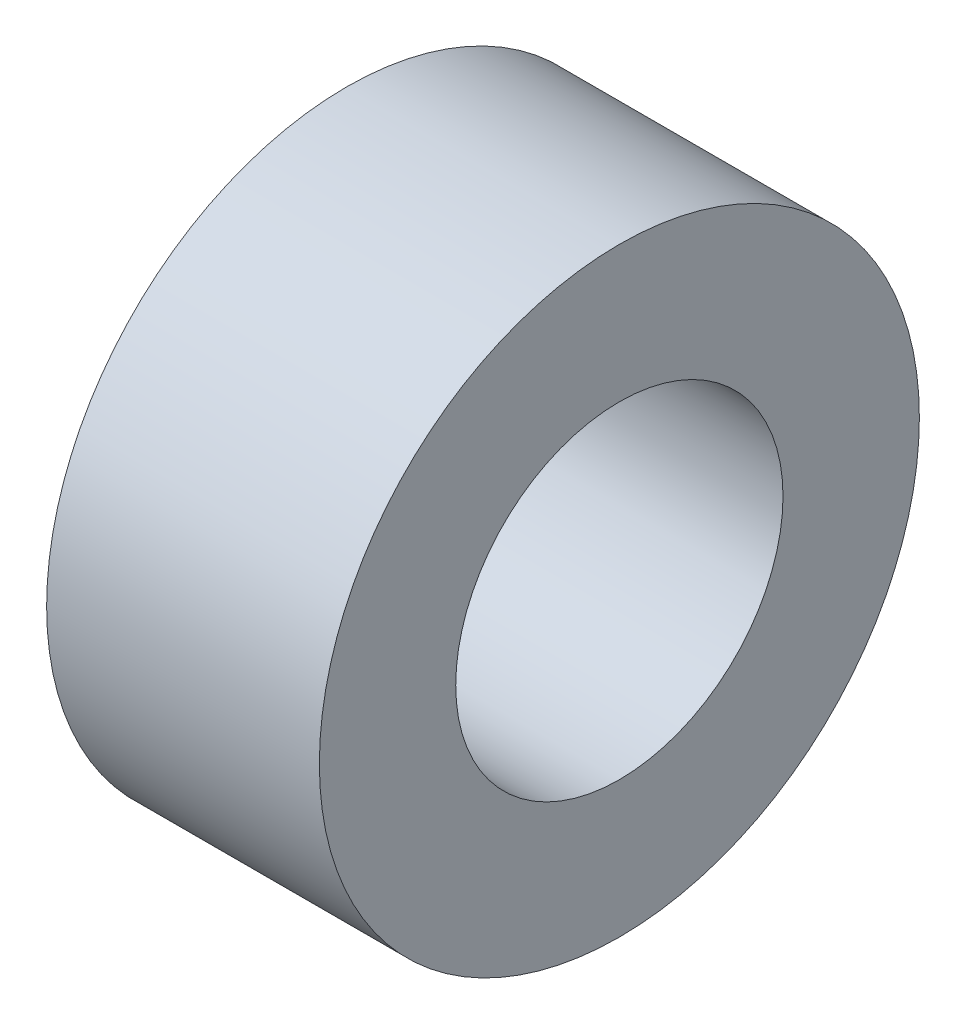
SolidWorks part; units mm, degrees
ref_plane "前视基准面" through (0, 0, 0) normal (0, 0, 1) x (1, 0, 0)
ref_plane "上视基准面" through (0, 0, 0) normal (0, 1, 0) x (1, 0, 0)
ref_plane "右视基准面" through (0, 0, 0) normal (1, 0, 0) x (0, 0, -1)
sketch "草图1" plane through (0, 0, 0) normal (1, 0, 0) x (0, 0, -1)
  circle A0 centre (0, 0) radius 3
  circle A1 centre (0, 0) radius 5.5
extrude "凸台-拉伸1" add sketch "草图1" along normal blind 5
